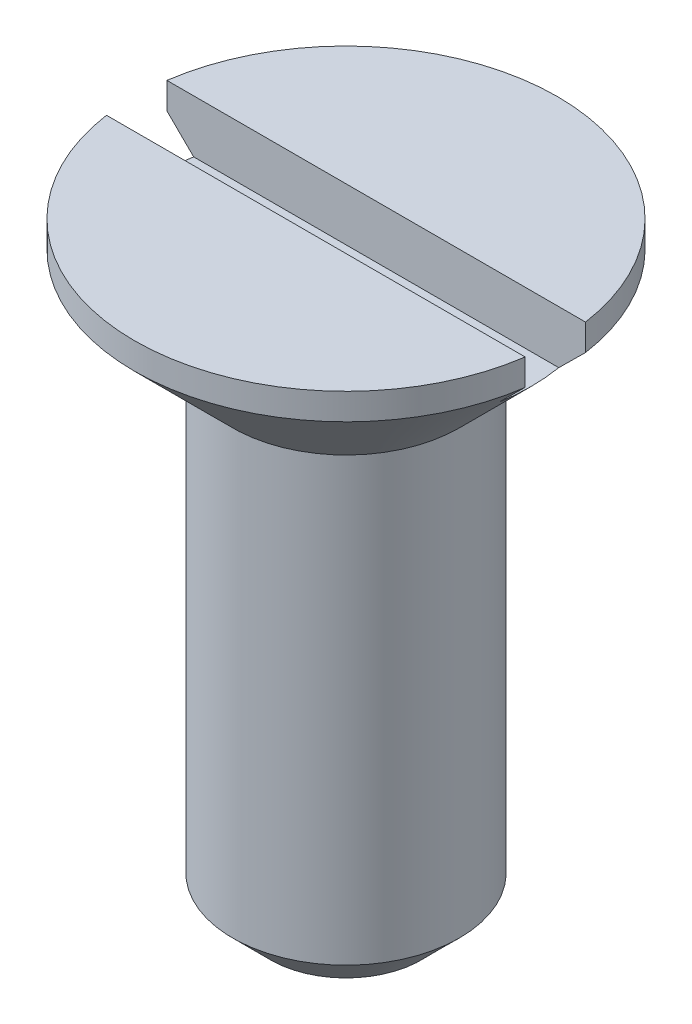
SolidWorks part; units mm, degrees
ref_plane "Спереди" through (0, 0, 0) normal (0, 0, 1) x (1, 0, 0)
ref_plane "Сверху" through (0, 0, 0) normal (0, 1, 0) x (1, 0, 0)
ref_plane "Справа" through (0, 0, 0) normal (1, 0, 0) x (0, 0, -1)
sketch "Эскиз1" plane through (0, 0, 0) normal (0, 0, 1) x (1, 0, 0)
  line L0 (0, 125.7632) -> (0, 0) construction
  line L2 (0, 92.035) -> (0, 84.035)
  line L3 (0, 92.035) -> (2.8, 92.035)
  line L4 (1.5, 90.385) -> (1.5, 84.035)
  line L5 (1.5, 90.385) -> (2.8, 91.685)
  line L6 (1.5, 84.035) -> (0, 84.035)
  line L7 (2.8, 92.035) -> (2.8, 91.685)
  dimension "D1" = 2.8
  dimension "D2" = 8
  dimension "D3" = 1.65
  dimension "D5" = 1.5
revolve "Повернуть1" add sketch "Эскиз1" angle 360 about L0
ref_axis "Ось4" through (0, 2.6135, 0) along (0, -1, 0)
sketch "Эскиз13" plane through (0, 92.035, 0) normal (0, 1, 0) x (-1, 0, 0)
  line L1 (2.8, -0.4) -> (-2.8, -0.4)
  line L2 (2.8, -0.4) -> (2.8, 0.4)
  line L3 (2.8, 0.4) -> (-2.8, 0.4)
  line L4 (-2.8, -0.4) -> (-2.8, 0.4)
  dimension "D1" = 2.8
  dimension "D2" = 5.6
  dimension "D3" = 0.4
  dimension "D4" = 0.8
extrude "Вырез-Вытянуть9" cut sketch "Эскиз13" against normal blind 0.7
chamfer "Фаска1" distance 0.5 angle 45 1 edges at (-1.5, 84.035, 0)
